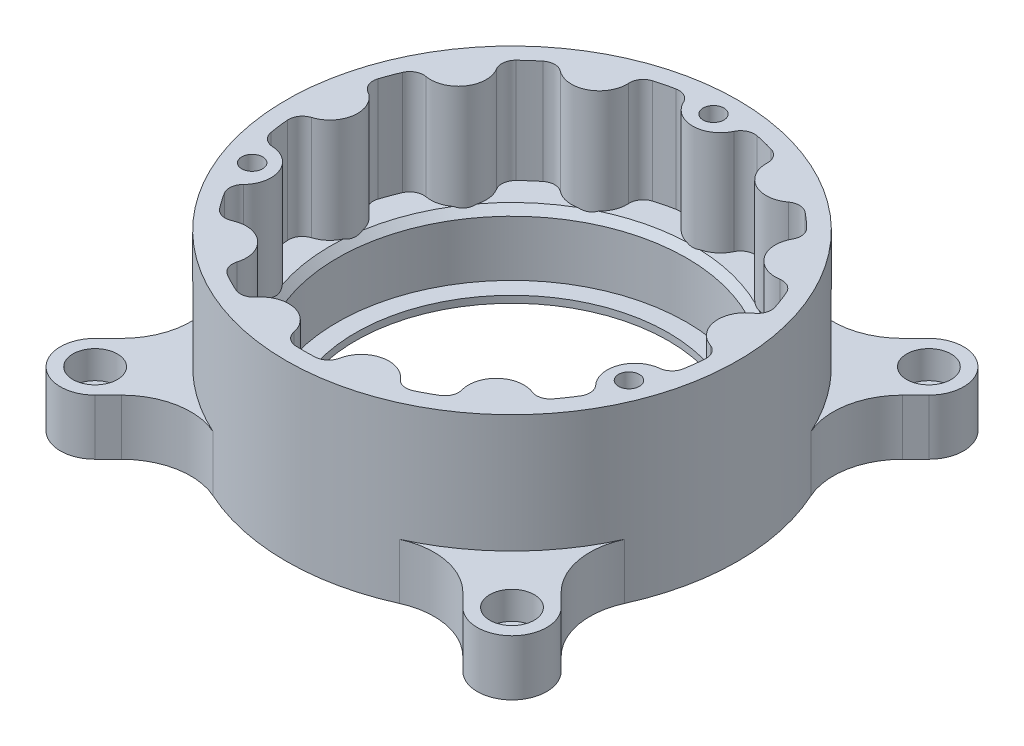
SolidWorks part; units mm, degrees
ref_plane "Front Plane" through (0, 0, 0) normal (0, 0, 1) x (1, 0, 0)
ref_plane "Top Plane" through (0, 0, 0) normal (0, 1, 0) x (1, 0, 0)
ref_plane "Right Plane" through (0, 0, 0) normal (1, 0, 0) x (0, 0, -1)
sketch "Sketch1" plane through (0, 0, 0) normal (0, 1, 0) x (1, 0, 0)
  circle A0 centre (0, 0) radius 32.5
  circle A1 centre (0, 0) radius 25.125
  dimension "D1" = 50.25
  dimension "D2" = 65
extrude "Boss-Extrude1" add sketch "Sketch1" along normal blind 9
sketch "Sketch2" plane through (0, 9, 0) normal (0, 1, 0) x (1, 0, 0)
  arc A2 (-25.3755, 12.9926) -> (-27.5762, 11.8133) centre (-25.7378, 11.0257) ccw
  arc A4 (-3.626, 28.3111) -> (3.626, 28.3111) centre (0, 30) ccw
  arc A5 (-5.8275, 29.4286) -> (-8.5144, 28.7664) centre (0, 0) ccw
  arc A6 (9.969, 26.7682) -> (16.359, 23.4158) centre (13.9663, 26.6213) ccw
  arc A7 (21.2717, 19.0918) -> (25.3606, 13.1841) centre (24.7627, 17.1392) ccw
  arc A8 (27.7083, 7.0615) -> (28.5939, -0.0494) centre (29.9159, 3.7259) ccw
  arc A9 (27.8305, -6.5674) -> (25.3247, -13.279) centre (28.2453, -10.5459) ccw
  arc A10 (21.625, -18.6949) -> (16.2843, -23.4938) centre (20.1336, -22.4065) ccw
  arc A11 (10.5031, -26.5673) -> (3.5177, -28.3507) centre (7.4392, -29.1389) ccw
  arc A12 (-3.0134, -28.387) -> (-10.0629, -26.714) centre (-6.9298, -29.2007) ccw
  arc A13 (-15.8477, -23.7184) -> (-21.3345, -18.9354) centre (-19.6817, -22.5779) ccw
  arc A14 (-25.0551, -13.6043) -> (-27.6892, -6.7929) centre (-27.8951, -10.7876) ccw
  arc A15 (-28.5019, -0.3507) -> (-27.6531, 6.9127) centre (-29.6885, 3.4693) ccw
  arc A16 (-25.3755, 12.9926) -> (-21.2399, 19.0156) centre (-24.651, 16.9265) ccw
  arc A17 (-16.3906, 23.3423) -> (-9.9434, 26.7328) centre (-13.9367, 26.5012) ccw
  arc A18 (-18.8759, 23.3174) -> (-20.9297, 21.493) centre (0, 0) ccw
  arc A19 (-27.5762, 11.8133) -> (-28.538, 9.2511) centre (0, 0) ccw
  arc A20 (-29.9021, -2.4221) -> (-29.5567, -5.138) centre (0, 0) ccw
  arc A21 (-25.3233, -16.0851) -> (-23.7439, -18.3365) centre (0, 0) ccw
  arc A22 (-14.9258, -26.0235) -> (-12.4601, -27.29) centre (0, 0) ccw
  arc A23 (-1.1306, -29.9787) -> (1.6681, -29.9536) centre (0, 0) ccw
  arc A24 (12.8947, -27.0874) -> (15.3853, -25.7545) centre (0, 0) ccw
  arc A25 (23.9685, -18.0419) -> (25.569, -15.6917) centre (0, 0) ccw
  arc A26 (29.5963, -4.9052) -> (29.9281, -2.0754) centre (0, 0) ccw
  arc A27 (28.5048, 9.3529) -> (27.4924, 12.0071) centre (0, 0) ccw
  arc A28 (20.9209, 21.5016) -> (18.8093, 23.3712) centre (0, 0) ccw
  arc A29 (8.5397, 28.7589) -> (5.8275, 29.4286) centre (0, 0) ccw
  circle A30 centre (0, 0) radius 32.5 construction
  circle A31 centre (0, 0) radius 32.5
  arc A32 (-27.6531, 6.9127) -> (-28.538, 9.2511) centre (-26.6354, 8.6344) cw
  arc A33 (-28.5019, -0.3507) -> (-29.9021, -2.4221) centre (-27.9086, -2.2606) ccw
  arc A34 (-27.6892, -6.7929) -> (-29.5567, -5.138) centre (-27.5863, -4.7955) cw
  arc A35 (-25.0551, -13.6043) -> (-25.3233, -16.0851) centre (-23.6351, -15.0127) ccw
  arc A36 (-21.3345, -18.9354) -> (-23.7439, -18.3365) centre (-22.161, -17.1141) cw
  arc A37 (-15.8477, -23.7184) -> (-14.9258, -26.0235) centre (-13.9307, -24.2886) ccw
  arc A38 (-10.0629, -26.714) -> (-12.4601, -27.29) centre (-11.6294, -25.4707) cw
  arc A39 (-3.0134, -28.387) -> (-1.1306, -29.9787) centre (-1.0553, -27.9801) ccw
  arc A40 (3.5177, -28.3507) -> (1.6681, -29.9536) centre (1.5569, -27.9567) cw
  arc A41 (10.5031, -26.5673) -> (12.8947, -27.0874) centre (12.035, -25.2816) ccw
  arc A42 (16.2843, -23.4938) -> (15.3853, -25.7545) centre (14.3596, -24.0375) cw
  arc A43 (21.625, -18.6949) -> (23.9685, -18.0419) centre (22.3706, -16.8391) ccw
  arc A44 (25.3247, -13.279) -> (25.569, -15.6917) centre (23.8644, -14.6456) cw
  arc A45 (27.8305, -6.5674) -> (29.5963, -4.9052) centre (27.6232, -4.5782) ccw
  arc A46 (28.5939, -0.0494) -> (29.9281, -2.0754) centre (27.9329, -1.937) cw
  arc A47 (27.7083, 7.0615) -> (28.5048, 9.3529) centre (26.6045, 8.7293) ccw
  arc A48 (25.3606, 13.1841) -> (27.4924, 12.0071) centre (25.6595, 11.2066) cw
  arc A49 (21.2717, 19.0918) -> (20.9209, 21.5016) centre (19.5261, 20.0681) ccw
  arc A50 (16.359, 23.4158) -> (18.8093, 23.3712) centre (17.5553, 21.8131) cw
  arc A51 (9.969, 26.7682) -> (8.5397, 28.7589) centre (7.9703, 26.8416) ccw
  arc A52 (3.626, 28.3111) -> (5.8275, 29.4286) centre (5.439, 27.4667) cw
  arc A53 (-3.626, 28.3111) -> (-5.8275, 29.4286) centre (-5.439, 27.4667) ccw
  arc A54 (-9.9434, 26.7328) -> (-8.5144, 28.7664) centre (-7.9468, 26.8486) cw
  arc A55 (-21.2399, 19.0156) -> (-20.9297, 21.493) centre (-19.5344, 20.0601) cw
  arc A56 (-16.3906, 23.3423) -> (-18.8759, 23.3174) centre (-17.6175, 21.7629) ccw
  point P45 (0.1292, -0.0211)
  dimension "D1" = 30
  dimension "D2" = 8
  dimension "D4" = 2
  dimension "D3" = 13
extrude "Boss-Extrude2" add sketch "Sketch2" along normal blind 15
sketch "Sketch3" plane through (0, 0, 0) normal (0, -1, 0) x (-1, 0, 0)
  circle A0 centre (0, 0) radius 32.5 construction
  circle A1 centre (0, 0) radius 32.5
  circle A2 centre (0, 0) radius 22.5
  dimension "D1" = 45
extrude "Boss-Extrude3" add sketch "Sketch3" along normal blind 1
sketch "Sketch6" plane through (0, -1, 0) normal (0, -1, 0) x (-1, 0, 0)
  circle A0 centre (0, -27.5) radius 1.5
  circle A1 centre (-19.4454, -19.4454) radius 1.5
  circle A2 centre (-27.5, 0) radius 1.5
  circle A3 centre (-19.4454, 19.4454) radius 1.5
  circle A4 centre (0, 27.5) radius 1.5
  circle A5 centre (19.4454, 19.4454) radius 1.5
  circle A6 centre (27.5, 0) radius 1.5
  circle A7 centre (19.4454, -19.4454) radius 1.5
  point P19 (0, 0)
  dimension "D2" = 3
  dimension "D1" = 27.5
  dimension "D3" = 8
extrude "Cut-Extrude1" cut sketch "Sketch6" against normal blind 8
chamfer "Chamfer1" distance 1 angle 45 1 edges at (0, 9, 25.125)
sketch "Sketch7" plane through (0, 24, 0) normal (0, 1, 0) x (1, 0, 0)
  circle A0 centre (0, 29) radius 1.5
  circle A1 centre (-27.1155, -10.2835) radius 1.5
  circle A2 centre (27.1155, -10.2835) radius 1.5
  dimension "D1" = 3
  dimension "D2" = 3
  dimension "D3" = 3
  dimension "D4" = 29
  dimension "D5" = 29
  dimension "D6" = 29
extrude "Cut-Extrude2" cut sketch "Sketch7" against normal blind 10
sketch "Sketch8" plane through (0, -1, 0) normal (0, -1, 0) x (1, 0, 0)
  line L0 (-33.5355, 26.4645) -> (-31.6536, 24.5825)
  line L1 (-26.4645, 33.5355) -> (-24.5825, 31.6536)
  line L2 (-30, 30) -> (0, 0) construction
  line L3 (26.4645, 33.5355) -> (24.5825, 31.6536)
  line L4 (33.5355, 26.4645) -> (31.6536, 24.5825)
  line L5 (33.5355, -26.4645) -> (31.6536, -24.5825)
  line L6 (26.4645, -33.5355) -> (24.5825, -31.6536)
  line L7 (-26.4645, -33.5355) -> (-24.5825, -31.6536)
  line L8 (-33.5355, -26.4645) -> (-31.6536, -24.5825)
  circle A1 centre (-30, 30) radius 2.2
  arc A2 (-26.4645, 33.5355) -> (-33.5355, 26.4645) centre (-30, 30) ccw
  circle A3 centre (0, 0) radius 32.5 construction
  arc A5 (-24.5825, 31.6536) -> (-13.3911, 29.613) centre (-17.5115, 38.7247) ccw
  arc A6 (-31.6536, 24.5825) -> (-29.613, 13.3911) centre (-38.7247, 17.5115) cw
  arc A7 (-13.3911, 29.613) -> (-29.613, 13.3911) centre (0, 0) ccw
  arc A8 (29.613, 13.3911) -> (13.3911, 29.613) centre (0, 0) ccw
  arc A9 (24.5825, 31.6536) -> (13.3911, 29.613) centre (17.5115, 38.7247) cw
  arc A10 (33.5355, 26.4645) -> (26.4645, 33.5355) centre (30, 30) ccw
  arc A11 (31.6536, 24.5825) -> (29.613, 13.3911) centre (38.7247, 17.5115) ccw
  circle A12 centre (30, 30) radius 2.2
  arc A13 (13.3911, -29.613) -> (29.613, -13.3911) centre (0, 0) ccw
  arc A14 (31.6536, -24.5825) -> (29.613, -13.3911) centre (38.7247, -17.5115) cw
  arc A15 (26.4645, -33.5355) -> (33.5355, -26.4645) centre (30, -30) ccw
  arc A16 (24.5825, -31.6536) -> (13.3911, -29.613) centre (17.5115, -38.7247) ccw
  circle A17 centre (30, -30) radius 2.2
  arc A18 (-29.613, -13.3911) -> (-13.3911, -29.613) centre (0, 0) ccw
  arc A19 (-24.5825, -31.6536) -> (-13.3911, -29.613) centre (-17.5115, -38.7247) cw
  arc A20 (-33.5355, -26.4645) -> (-26.4645, -33.5355) centre (-30, -30) ccw
  arc A21 (-31.6536, -24.5825) -> (-29.613, -13.3911) centre (-38.7247, -17.5115) ccw
  circle A22 centre (-30, -30) radius 2.2
  point P11 (-19.1718, 26.2429)
  point P14 (-26.2429, 19.1718)
  point P48 (0, 0)
  dimension "D1" = 30
  dimension "D3" = 4.4
  dimension "D4" = 10
  dimension "D5" = 10
  dimension "D2" = 30
  dimension "D6" = 4
extrude "Boss-Extrude4" add sketch "Sketch8" against normal blind 8
sketch "Sketch9" plane through (0, 7, 0) normal (0, 1, 0) x (1, 0, 0)
  circle A0 centre (-30, -30) radius 2.2 construction
  circle A1 centre (30, -30) radius 2.2 construction
  circle A2 centre (30, 30) radius 2.2 construction
  circle A3 centre (-30, 30) radius 2.2 construction
  circle A4 centre (-30, -30) radius 2.2
  circle A5 centre (30, -30) radius 2.2
  circle A6 centre (30, 30) radius 2.2
  circle A7 centre (-30, 30) radius 2.2
  circle A8 centre (-30, -30) radius 3.2
  circle A9 centre (30, -30) radius 3.2
  circle A10 centre (30, 30) radius 3.2
  circle A11 centre (-30, 30) radius 3.2
  dimension "D1" = 1
extrude "Cut-Extrude3" cut sketch "Sketch9" against normal blind 4
